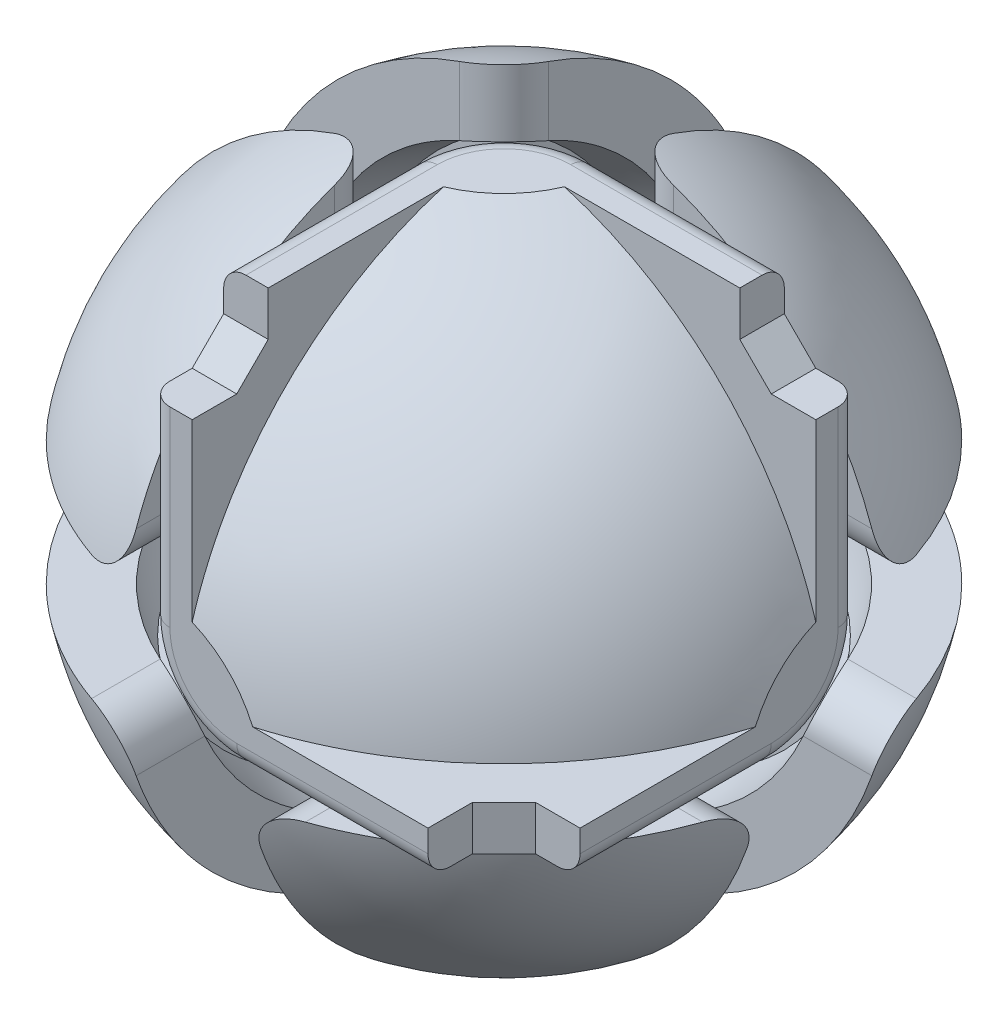
SolidWorks part; units mm, degrees
ref_plane "Front Plane" through (0, 0, 0) normal (1, 0, 0) x (0, 1, 0)
ref_plane "Top Plane" through (0, 0, 0) normal (0, 0, 1) x (0, 1, 0)
ref_plane "Right Plane" through (0, 0, 0) normal (0, 1, 0) x (-1, 0, 0)
sketch "Sketch1" plane through (0, 0, 0) normal (1, 0, 0) x (0, 1, 0)
  line L0 (0, 37) -> (0, -37)
  arc A0 (0, -37) -> (0, 37) centre (0, 0) ccw
  dimension "D1" = 74
revolve "Revolve1" add sketch "Sketch1" angle 360 about L0
sketch "Sketch2" plane through (0, 0, 0) normal (1, 0, 0) x (0, 1, 0)
  line L0 (0, 0) -> (0, 37) construction
  line L1 (-7, 36.3318) -> (-7, 29.1719)
  line L2 (7, 36.3318) -> (7, 29.1719)
  line L5 (-12, 27.4955) -> (-12, 19.6214)
  line L6 (0, 0) -> (37, 0) construction
  line L7 (12, 27.4955) -> (12, 19.6214)
  arc A0 (12, 27.4955) -> (7, 29.1719) centre (0, 0) ccw
  arc A1 (12, 19.6214) -> (-12, 19.6214) centre (0, 0) ccw
  circle A2 centre (0, 0) radius 37 construction
  arc A3 (7, 36.3318) -> (-7, 36.3318) centre (0, 0) ccw
  arc A4 (-7, 29.1719) -> (-12, 27.4955) centre (0, 0) ccw
  dimension "D3" = 60
  dimension "D4" = 46
  dimension "D1" = 7
  dimension "D2" = 7
  dimension "D5" = 12
  dimension "D6" = 12
revolve "Cut-Revolve1" cut sketch "Sketch2" angle 360 about L6
sketch "Sketch3" plane through (0, 0, 0) normal (1, 0, 0) x (0, 1, 0)
  line L0 (0, 0) -> (0, 36.4522) construction
pattern_circular "CirPattern1" count 2 every 90 about axis through (0, 0, 0) along (0, 0, 1) of "Cut-Revolve1" reverse direction yes
sketch "Sketch5" plane through (0, 0, 0) normal (0, 1, 0) x (-1, 0, 0)
  line L0 (0, 0) -> (41.2324, 0) construction
pattern_circular "CirPattern2" count 2 every 90 about axis through (0, 0, 0) along (-1, 0, 0) of "Cut-Revolve1" reverse direction yes
sketch "Sketch6" plane through (0, 0, 0) normal (0, 0, 1) x (0, 1, 0)
  line L1 (0, 0) -> (40, 0)
  line L2 (0, 0) -> (0, -40)
  line L3 (0, -40) -> (40, -40)
  line L4 (40, 0) -> (40, -40)
  dimension "D1" = 40
  dimension "D2" = 40
extrude "Boss-Extrude1" add sketch "Sketch6" along normal blind 40
fillet "Fillet2" [suppressed] radius 5
fillet "Fillet3" [suppressed] radius 2.5
sketch "Sketch7" plane through (0, 0, 0) normal (0, -1, 0) x (1, 0, 0)
  line L1 (98.3669, 42) -> (7, 42)
  line L2 (0, 42) -> (0, 0) construction
  line L3 (7, 42) -> (7, 41.4126)
  line L4 (7, 35.6511) -> (7, 7) construction
  line L5 (42, 0) -> (98.3669, 0)
  line L6 (98.3669, 0) -> (98.3669, 42)
  arc A0 (42, 0) -> (7, 41.4126) centre (0, 0) ccw
  dimension "D1" = 84
revolve "Cut-Revolve5" cut sketch "Sketch7" angle 90 about L2 reverse direction yes
sketch "Sketch8" plane through (0, 0, 0) normal (0, -1, 0) x (1, 0, 0)
  line L0 (40, 12.8062) -> (40, 0) construction
  line L1 (0, 0) -> (40, 0)
  line L2 (0, 0) -> (0, 40)
  line L3 (0, 40) -> (31.4645, 40)
  line L4 (40, 0) -> (40, 31.4645)
  line L5 (0, 40) -> (12.8062, 40) construction
  line L6 (31.4645, 40) -> (31.4645, 35)
  line L7 (31.4645, 35) -> (35, 31.4645)
  line L8 (35, 31.4645) -> (40, 31.4645)
  dimension "D1" = 5
  dimension "D2" = 135
extrude "Boss-Extrude2" add sketch "Sketch8" against normal blind 5
sketch "Sketch9" plane through (0, 0, 0) normal (0, 0, -1) x (1, 0, 0)
  line L0 (40, 0) -> (40, -12.8062) construction
  line L1 (0, 0) -> (40, 0)
  line L2 (0, 0) -> (0, -40)
  line L3 (0, -40) -> (31.4645, -40)
  line L4 (40, 0) -> (40, -31.4645)
  line L5 (12.8062, -40) -> (0, -40) construction
  line L6 (31.4645, -40) -> (31.4645, -35)
  line L7 (31.4645, -35) -> (35, -31.4645)
  line L8 (35, -31.4645) -> (40, -31.4645)
  dimension "D1" = 5
  dimension "D2" = 135
extrude "Boss-Extrude3" add sketch "Sketch9" against normal blind 5
sketch "Sketch10" plane through (0, 0, 0) normal (-1, 0, 0) x (0, -1, 0)
  line L0 (-12.8062, 40) -> (0, 40) construction
  line L1 (0, 0) -> (-40, 0)
  line L2 (0, 0) -> (0, 40)
  line L3 (0, 40) -> (-31.4645, 40)
  line L4 (-40, 0) -> (-40, 31.4645)
  line L5 (-40, 12.8062) -> (-40, 0) construction
  line L6 (-31.4645, 40) -> (-31.4645, 35)
  line L7 (-31.4645, 35) -> (-35, 31.4645)
  line L8 (-35, 31.4645) -> (-40, 31.4645)
  dimension "D1" = 5
  dimension "D2" = 135
extrude "Boss-Extrude4" add sketch "Sketch10" against normal blind 5
fillet "Fillet4" radius 10 3 edges at (0, 31.5, 0) (31.5, 0, 0) (0, 0, 31.5)
fillet "Fillet5" radius 2.5 9 edges at (20.7322, 40, 0) (0, 40, 20.7322) (40, 0, 20.7322) (40, 20.7322, 0) (0, 20.7322, 40) (2.9289, 2.9289, 40) (2.9289, 40, 2.9289) (40, 2.9289, 2.9289) (20.7322, 0, 40)
fillet "Fillet6" radius 5 21 edges at (7, -7, -31.9853) (7, -7, 31.9853) (7, -31.9853, 7) (-7, 31.9853, 7) (-7, -31.9853, 7) (-7, 7, -31.9853) (-7, 7, 31.9853) (-31.9853, 7, 7) (-7, -7, -31.9853) (-7, -7, 31.9853) (-31.9853, -7, 7) (31.9853, -7, 7) (7, 7, -31.9853) (-31.9853, 7, -7) (31.9853, 7, -7) (7, 31.9853, -7) (7, -31.9853, -7) (-7, -31.9853, -7) (-7, 31.9853, -7) (-31.9853, -7, -7) (31.9853, -7, -7)
ref_plane "Plane3" through (17.313, -17.313, 17.313) normal (0.5774, -0.5774, 0.5774) x (-0.8165, -0.4082, 0.4082)
ref_plane "Plane4" through (19.0451, -19.0451, 19.0451) normal (0.5774, -0.5774, 0.5774) x (-0.8165, -0.4082, 0.4082)
sketch "Sketch12" plane through (19.0451, -19.0451, 19.0451) normal (0.5774, -0.5774, 0.5774) x (-0.8165, -0.4082, 0.4082)
  line L0 (0, 5) -> (0, -5)
  arc A0 (0, -5) -> (0, 5) centre (0, 0) ccw
  dimension "D1" = 10
revolve "Revolve3" [suppressed] add sketch "Sketch12" angle 360 about L0
mirror "Mirror1" [suppressed] about plane through (0, 0, 0) normal (1, 0, 0) second plane through (0, 0, 0) second plane normal (0, 0, 1)
mirror "Mirror2" [suppressed] about plane through (0, 0, 0) normal (0, 1, 0)
